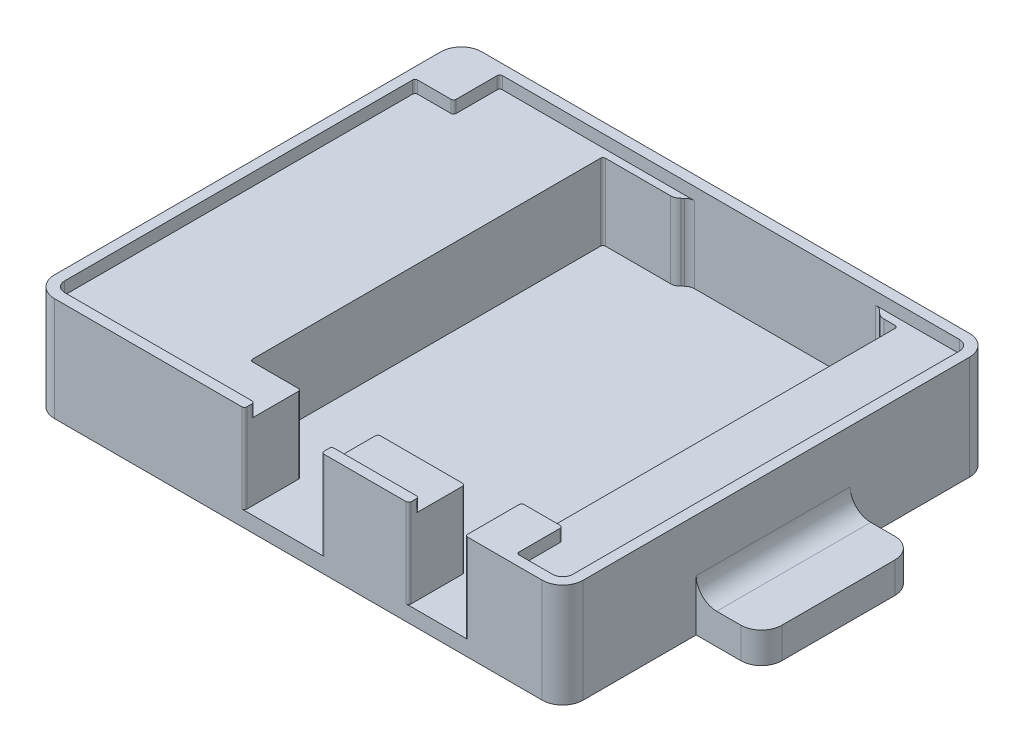
SolidWorks part; units mm, degrees
ref_plane "Front Plane" through (0, 0, 0) normal (0, 0, 1) x (1, 0, 0)
ref_plane "Top Plane" through (0, 0, 0) normal (0, 1, 0) x (1, 0, 0)
ref_plane "Right Plane" through (0, 0, 0) normal (1, 0, 0) x (0, 0, -1)
sketch "Sketch1" plane through (0, 0, 0) normal (0, 1, 0) x (1, 0, 0)
  line L1 (0, 0) -> (103, 0)
  line L2 (0, 0) -> (0, 83.25)
  line L3 (0, 83.25) -> (103, 83.25)
  line L4 (103, 0) -> (103, 83.25)
  dimension "D1" = 83.25
  dimension "D2" = 103
extrude "Boss-Extrude1" add sketch "Sketch1" along normal blind 20.2438
sketch "Sketch2" plane through (0, 20.2438, 0) normal (0, 1, 0) x (1, 0, 0)
  line L0 (0, 83.25) -> (0, 0) construction
  line L1 (31.1, 79.75) -> (45.1, 79.75)
  line L2 (31.1, 79.75) -> (31.1, 11)
  line L3 (31.1, 11) -> (88.5, 11)
  line L4 (88.5, 79.75) -> (88.5, 11)
  line L5 (103, 83.25) -> (0, 83.25) construction
  line L6 (85, 79.75) -> (88.5, 79.75)
  line L8 (45.85, 80.5) -> (45.85, 81.25) construction
  line L9 (46.6, 81.25) -> (83.5, 81.25)
  line L10 (84.25, 80.5) -> (84.25, 81.25) construction
  line L11 (103, 0) -> (103, 83.25) construction
  line L12 (45.1, 79.75) -> (46.6, 81.25)
  line L13 (85, 79.75) -> (83.5, 81.25)
  line L14 (84.25, 79.75) -> (84.25, 80.5) construction
  line L15 (84.25, 79.75) -> (85, 79.75) construction
  line L16 (83.5, 81.25) -> (84.25, 81.25) construction
  line L17 (45.1, 79.75) -> (45.85, 79.75) construction
  line L18 (45.85, 79.75) -> (45.85, 80.5) construction
  line L19 (45.85, 81.25) -> (46.6, 81.25) construction
  point P18 (84.25, 80.5)
  point P19 (45.85, 80.5)
  dimension "D1" = 31.1
  dimension "D2" = 3.5
  dimension "D3" = 2
  dimension "D4" = 14.75
  dimension "D5" = 4.25
  dimension "D6" = 68.75
  dimension "D7" = 14.5
  dimension "D8" = 38.4
  dimension "D9" = 45
  dimension "D10" = 45
extrude "Cut-Extrude1" cut sketch "Sketch2" against normal offset from surface (17.2438 mm away) 3 up to face at (51.5, 0, -41.625)
sketch "Sketch3" plane through (0, 0, 0) normal (0, 0, 1) x (1, 0, 0)
  line L0 (0, 20.2438) -> (103, 20.2438) construction
  line L1 (41, 20.2438) -> (56, 20.2438)
  line L2 (41, 20.2438) -> (41, 3)
  line L3 (41, 3) -> (56, 3)
  line L4 (56, 20.2438) -> (56, 3)
  line L5 (0, 20.2438) -> (0, 0) construction
  line L6 (73, 20.2438) -> (84, 20.2438)
  line L7 (73, 20.2438) -> (73, 3)
  line L8 (73, 3) -> (84, 3)
  line L9 (84, 20.2438) -> (84, 3)
  line L10 (31.1, 3) -> (88.5, 3) construction
  dimension "D1" = 17.2438
  dimension "D2" = 15
  dimension "D3" = 41
  dimension "D4" = 11
  dimension "D6" = 17
extrude "Cut-Extrude2" cut sketch "Sketch3" against normal blind 14.9225
sketch "Sketch4" plane through (0, 20.2438, 0) normal (0, 1, 0) x (1, 0, 0)
  line L0 (0, 83.25) -> (0, 0) construction
  line L1 (9.5, 81.25) -> (101, 81.25)
  line L2 (2, 72.25) -> (2, 2)
  line L3 (2, 2) -> (84, 2)
  line L4 (101, 81.25) -> (101, 2)
  line L5 (0, 0) -> (41, 0) construction
  line L6 (2, 72.25) -> (9.5, 72.25)
  line L7 (9.5, 72.25) -> (9.5, 81.25)
  line L8 (92, 2) -> (92, 11)
  line L9 (92, 11) -> (84, 11)
  line L10 (84, 11) -> (84, 2)
  line L11 (84, 11) -> (84, 0) construction
  line L12 (92, 2) -> (101, 2)
  line L13 (103, 0) -> (103, 83.25) construction
  line L14 (103, 83.25) -> (0, 83.25) construction
  dimension "D1" = 2
  dimension "D2" = 2
  dimension "D3" = 2
  dimension "D4" = 2
  dimension "D5" = 9.5
  dimension "D6" = 11
  dimension "D7" = 8
  dimension "D8" = 11
  dimension "D9" = 19
extrude "Cut-Extrude3" cut sketch "Sketch4" against normal blind 2.4
sketch "Sketch5" plane through (0, 0, 0) normal (-1, 0, 0) x (0, 0, 1)
  line L0 (-83.25, 0) -> (0, 0) construction
  line L1 (-56, 0) -> (-26, 0)
  line L2 (-56, 0) -> (-56, 6)
  line L3 (-56, 6) -> (-26, 6)
  line L4 (-26, 0) -> (-26, 6)
  line L6 (0, 20.2438) -> (0, 0) construction
  dimension "D1" = 30
  dimension "D2" = 26
  dimension "D3" = 6
extrude "Boss-Extrude2" add sketch "Sketch5" along normal blind 12.7
ref_plane "Plane1" through (51.5, 0, 0) normal (-1, 0, 0) x (0, 0, 1)
mirror "Mirror1" about plane through (51.5, 0, 0) normal (-1, 0, 0) of "Boss-Extrude2"
sketch "Sketch6" plane through (0, 0, -83.25) normal (0, 0, -1) x (-1, 0, 0)
  line L0 (-103, 0) -> (0, 0) construction
  line L1 (-66.5, 0) -> (-36.5, 0)
  line L2 (-66.5, 0) -> (-66.5, 6)
  line L3 (-66.5, 6) -> (-36.5, 6)
  line L4 (-36.5, 0) -> (-36.5, 6)
  line L6 (-66.5, 0) -> (-36.5, 6) construction
  line L7 (-51.5, -11.1341) -> (-51.5, 11.1341) construction
  point P8 (-51.5, 3)
  dimension "D1" = 30
  dimension "D2" = 6
extrude "Boss-Extrude3" add sketch "Sketch6" along normal blind 12.7
fillet "Fillet1" radius 4 4 edges at (103, 10.1219, 0) (103, 10.1219, -83.25) (0, 10.1219, -83.25) (0, 10.1219, 0)
fillet "Fillet2" radius 0.5 20 edges at (41, 10.4219, -11) (56, 10.4219, -11) (73, 10.4219, -11) (92, 19.0438, -11) (84, 11.6219, -11) (9.5, 19.0438, -72.25) (84, 11.6219, 0) (56, 19.0438, -2) (41, 19.0438, -2) (73, 19.0438, -2) (73, 11.6219, 0) (56, 11.6219, 0) (41, 11.6219, 0) (92, 19.0438, -2) (9.5, 19.0438, -81.25) (2, 19.0438, -72.25) (88.5, 10.4219, -11) (31.1, 10.4219, -11) (31.1, 10.4219, -79.75) (88.5, 10.4219, -79.75)
fillet "Fillet3" radius 2 3 edges at (101, 19.0438, -81.25) (101, 19.0438, -2) (2, 19.0438, -2)
fillet "Fillet4" radius 4 9 edges at (0, 6, -41) (51.5, 6, -83.25) (103, 6, -41) (115.7, 3, -26) (115.7, 3, -56) (66.5, 3, -95.95) (36.5, 3, -95.95) (-12.7, 3, -56) (-12.7, 3, -26)
fillet "Fillet5" radius 2 4 edges at (45.1, 10.4219, -79.75) (46.6, 10.4219, -81.25) (85, 10.4219, -79.75) (83.5, 10.4219, -81.25)
